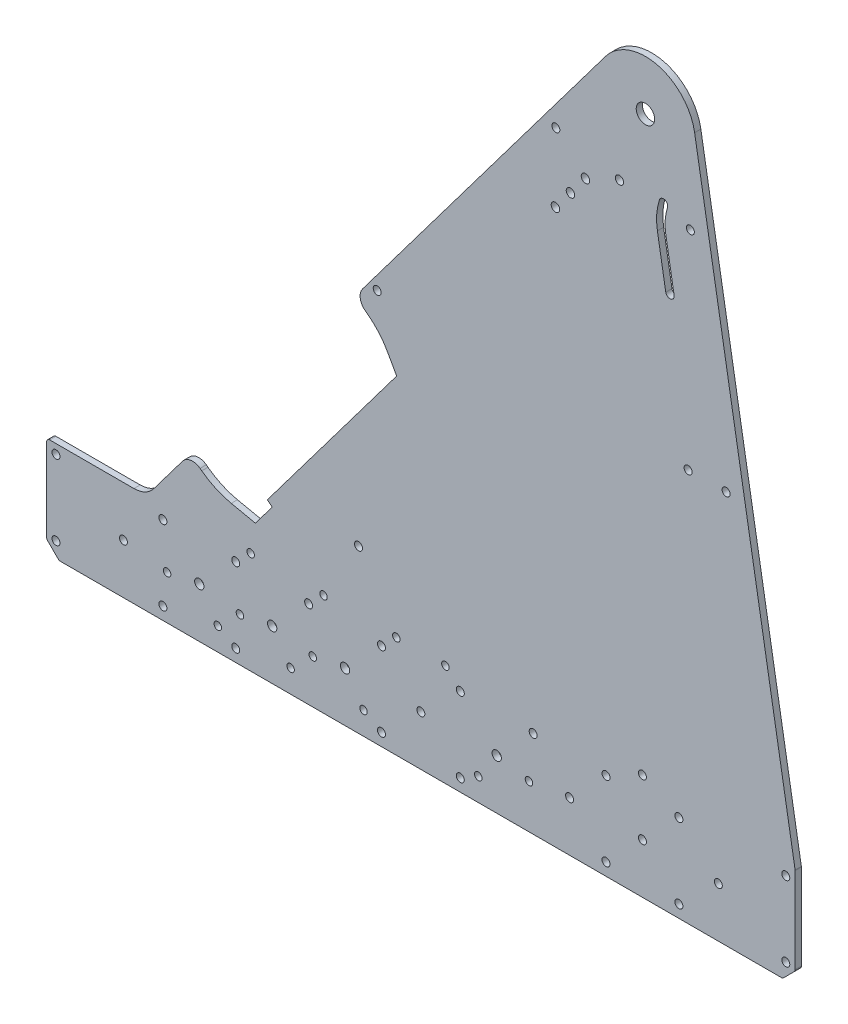
SolidWorks part; units mm, degrees
ref_plane "Front Plane" through (0, 0, 0) normal (0, 0, 1) x (1, 0, 0)
ref_plane "Top Plane" through (0, 0, 0) normal (0, 1, 0) x (1, 0, 0)
ref_plane "Right Plane" through (0, 0, 0) normal (1, 0, 0) x (0, 0, -1)
sketch "Sketch1" plane through (0, 0, 0) normal (0, 0, 1) x (1, 0, 0)
  line L1 (0, 0) -> (381, 0)
  line L2 (0, 0) -> (0, 50.8)
  line L4 (381, 0) -> (381, 50.8)
  line L5 (381, 50.8) -> (329.8374, 350.3513)
  line L6 (0, 50.8) -> (44.463, 50.8)
  line L7 (54.6105, 55.8634) -> (73.025, 80.3327)
  line L9 (112.3265, 79.755) -> (178.1676, 167.245)
  line L11 (157.0275, 191.9556) -> (284.5049, 361.3482)
  line L12 (112.3265, 79.755) -> (114.8634, 77.8458)
  line L13 (114.8634, 77.8458) -> (106.2722, 66.4299)
  line L14 (157.0275, 191.9556) -> (169.7119, 182.4098)
  line L15 (169.7119, 182.4098) -> (178.1676, 167.245)
  line L16 (73.025, 80.3327) -> (85.7094, 70.7869)
  line L17 (85.7094, 70.7869) -> (106.2722, 66.4299)
  line L18 (169.7119, 182.4098) -> (85.7094, 70.7869) construction
  arc A0 (284.5049, 361.3482) -> (329.8374, 350.3513) centre (304.8, 346.075) cw
  arc A1 (44.463, 50.8) -> (54.6105, 55.8634) centre (44.463, 63.5) ccw
  point P11 (50.8, 50.8)
  dimension "D4" = 346.075
  dimension "D7" = 12.7
  dimension "D5" = 25.4
  dimension "D1" = 50.8
  dimension "D2" = 381
  dimension "D3" = 76.2
  dimension "D6" = 50.8
  dimension "D8" = 123.825
  dimension "D9" = 139.7
  dimension "D10" = 15.875
  dimension "D11" = 31.75
  dimension "D12" = 73.025
  dimension "D13" = 3.175
  dimension "D14" = 14.2875
  dimension "D15" = 115
extrude "Boss-Extrude1" add sketch "Sketch1" along normal blind 3.175
sketch "Sketch2" plane through (0, 0, 3.175) normal (0, 0, 1) x (1, 0, 0)
  line L1 (190.5, 50.8) -> (190.5, 0) construction
  line L3 (0, 0) -> (381, 0) construction
  line L5 (0, 6.35) -> (0, 0)
  line L6 (0, 50.8) -> (0, 0) construction
  line L7 (0, 0) -> (6.35, 0)
  line L8 (6.35, 0) -> (0, 6.35)
  line L9 (381, 0) -> (374.65, 0)
  line L10 (374.65, 0) -> (381, 6.35)
  line L11 (381, 6.35) -> (381, 0)
  circle A19 centre (4.7625, 46.0375) radius 2.032
  circle A20 centre (4.7625, 7.9375) radius 2.032
  circle A21 centre (376.2375, 7.9375) radius 2.032
  circle A22 centre (376.2375, 46.0375) radius 2.032
  dimension "D21" = 6.35
  dimension "D27" = 4.064
  dimension "D4" = 46.0375
  dimension "D22" = 6.35
  dimension "D25" = 4.7625
  dimension "D28" = 7.9375
extrude "Cut-Extrude1" cut sketch "Sketch2" against normal up to next
sketch "Sketch5" plane through (0, 0, 3.175) normal (0, 0, 1) x (1, 0, 0)
  line L0 (151.892, 25.4) -> (229.108, 25.4) construction
  line L1 (229.108, 25.4) -> (341.884, 25.4) construction
  circle A0 centre (39.116, 25.4) radius 2.032
  circle A1 centre (59.182, 6.35) radius 2.032
  circle A2 centre (59.182, 44.45) radius 2.032
  circle A3 centre (96.266, 44.45) radius 2.032
  circle A4 centre (133.35, 44.45) radius 2.032
  circle A5 centre (170.434, 44.45) radius 2.032
  circle A6 centre (210.566, 44.45) radius 2.032
  circle A7 centre (210.566, 6.35) radius 2.032
  circle A8 centre (170.434, 6.35) radius 2.032
  circle A9 centre (247.65, 44.45) radius 2.032
  circle A10 centre (266.192, 25.4) radius 2.032
  circle A11 centre (39.116, 25.4) radius 2.286 construction
  circle A12 centre (59.182, 44.45) radius 1.905 construction
  circle A13 centre (59.182, 6.35) radius 1.905 construction
  circle A14 centre (96.266, 44.45) radius 1.905 construction
  circle A15 centre (133.35, 44.45) radius 1.905 construction
  circle A16 centre (170.434, 44.45) radius 1.905 construction
  circle A17 centre (170.434, 6.35) radius 2.159 construction
  circle A18 centre (210.566, 6.35) radius 2.159 construction
  circle A19 centre (210.566, 44.45) radius 1.905 construction
  circle A20 centre (247.65, 44.45) radius 1.905 construction
  circle A21 centre (266.192, 25.4) radius 2.286 construction
  circle A22 centre (77.724, 25.4) radius 2.3813
  circle A23 centre (114.808, 25.4) radius 2.3813
  circle A24 centre (151.892, 25.4) radius 2.3813
  circle A25 centre (229.108, 25.4) radius 2.3813
  circle A26 centre (190.5, 25.4) radius 2.032
  circle A28 centre (303.276, 25.4) radius 2.032
  circle A29 centre (341.884, 25.4) radius 2.032
  circle A30 centre (77.724, 25.4) radius 7.366 construction
  circle A31 centre (114.808, 25.4) radius 7.366 construction
  circle A32 centre (151.892, 25.4) radius 7.366 construction
  circle A33 centre (229.108, 25.4) radius 7.366 construction
  dimension "D1" = 4.064
  dimension "D2" = 4.7625
  dimension "D3" = 37.084
  dimension "D4" = 38.608
  dimension "D5" = 38.608
extrude "Cut-Extrude4" cut sketch "Sketch5" against normal through all
sketch "Sketch6" plane through (0, 0, 3.175) normal (0, 0, 1) x (1, 0, 0)
  line L0 (6.35, 0) -> (374.65, 0) construction
  line L1 (266.192, 25.4) -> (303.276, 25.4) construction
  line L2 (284.734, 6.35) -> (284.734, 44.45) construction
  line L3 (151.892, 25.4) -> (114.808, 25.4) construction
  line L4 (114.808, 25.4) -> (77.724, 25.4) construction
  circle A0 centre (284.734, 44.45) radius 2.032
  circle A1 centre (284.734, 6.35) radius 2.032
  circle A2 centre (321.818, 6.35) radius 2.032
  circle A3 centre (321.818, 44.45) radius 2.032
  circle A4 centre (96.266, 6.35) radius 2.032
  circle A6 centre (303.276, 53.975) radius 2.032
  arc A7 (304.329, 52.3875) -> (302.223, 52.3875) centre (303.276, 53.975) ccw construction
  point P8 (284.734, 25.4)
  point P9 (284.734, 25.4)
  point P28 (96.266, 25.4)
  dimension "D1" = 4.064
  dimension "D2" = 6.35
  dimension "D3" = 37.084
extrude "Cut-Extrude5" cut sketch "Sketch6" against normal through all
sketch "Sketch3" plane through (0, 0, 3.175) normal (0, 0, 1) x (1, 0, 0)
  line L0 (73.025, 80.3327) -> (54.6105, 55.8634) construction
  line L1 (381, 6.35) -> (381, 50.8) construction
  line L2 (6.35, 0) -> (374.65, 0) construction
  line L3 (304.8, 346.075) -> (291.577, 310.3432) construction
  line L4 (274.2689, 302.3851) -> (291.577, 310.3432) construction
  line L5 (274.2689, 302.3851) -> (266.6323, 292.2376) construction
  line L6 (266.6323, 292.2376) -> (258.9957, 282.09) construction
  line L7 (381, 50.8) -> (329.8374, 350.3513) construction
  line L9 (0, 50.8) -> (0, 6.35) construction
  line L14 (284.5049, 361.3482) -> (157.0275, 191.9556) construction
  line L15 (317.2725, 273.05) -> (310.5324, 312.5124) construction
  line L16 (315.1443, 272.6865) -> (310.8903, 297.5932)
  line L17 (319.4007, 273.4135) -> (315.1467, 298.3202)
  circle A0 centre (304.8, 346.075) radius 4.699
  circle A1 centre (168.275, 200.025) radius 2.032
  circle A2 centre (158.75, 82.55) radius 2.032
  circle A3 centre (291.577, 310.3432) radius 2.0955
  circle A5 centre (274.2689, 302.3851) radius 2.159
  circle A6 centre (266.6323, 292.2376) radius 2.159
  circle A7 centre (258.9957, 282.09) radius 2.159
  circle A8 centre (327.6754, 306.4341) radius 2.032
  circle A9 centre (345.8498, 200.025) radius 2.032
  circle A12 centre (259.2118, 317.1783) radius 2.032
  circle A13 centre (326.524, 200.025) radius 2.032
  arc A14 (315.1467, 298.3202) -> (316.0385, 310.4799) centre (340.1841, 302.5965) cw
  arc A19 (315.1443, 272.6865) -> (319.4007, 273.4135) centre (317.2725, 273.05) ccw
  arc A21 (316.0385, 310.4799) -> (311.9337, 311.8201) centre (313.9861, 311.15) ccw
  arc A22 (311.9337, 311.8201) -> (310.8903, 297.5932) centre (340.1841, 302.5965) ccw
  point P41 (313.3855, 298.45)
  dimension "D1" = 9.398
  dimension "D3" = 4.064
  dimension "D6" = 4.064
  dimension "D11" = 4.318
  dimension "D10" = 4.191
  dimension "D13" = 4.064
  dimension "D20" = 4.064
  dimension "D18" = 3.175
  dimension "D34" = 4.318
  dimension "D21" = 25.4
  dimension "D4" = 222.25
  dimension "D5" = 82.55
  dimension "D7" = 19.05
  dimension "D8" = 12.7
  dimension "D9" = 38.1
  dimension "D12" = 12.7
  dimension "D14" = 9.525
  dimension "D15" = 9.525
  dimension "D16" = 107.95
  dimension "D17" = 200.025
  dimension "D19" = 34.925
  dimension "D23" = 53.975
  dimension "D24" = 6.35
  dimension "D25" = 200.025
  dimension "D26" = 168.275
  dimension "D27" = 28.575
  dimension "D30" = 30
  dimension "D31" = 135
  dimension "D33" = 25.4
  dimension "D35" = 273.05
extrude "Cut-Extrude2" cut sketch "Sketch3" against normal through all
fillet "Fillet1" radius 1.5875 6 edges at (374.65, 0, 1.5875) (381, 6.35, 1.5875) (381, 50.8, 1.5875) (6.35, 0, 1.5875) (0, 6.35, 1.5875) (0, 50.8, 1.5875)
sketch "Sketch4" plane through (0, 0, 0) normal (0, 0, -1) x (-1, 0, 0)
  circle A0 centre (-61.3181, 22.2981) radius 1.905 construction
  circle A1 centre (-87.1313, 11.606) radius 1.905 construction
  circle A2 centre (-98.4021, 22.2981) radius 1.905 construction
  circle A3 centre (-124.2153, 11.606) radius 1.905 construction
  circle A4 centre (-135.4861, 22.2981) radius 1.905 construction
  circle A5 centre (-161.2993, 11.606) radius 1.905 construction
  circle A6 centre (-245.5139, 22.2981) radius 1.905 construction
  circle A7 centre (-219.7007, 11.606) radius 1.905 construction
  circle A8 centre (-202.982, 51.9684) radius 1.905 construction
  circle A9 centre (-178.018, 51.9684) radius 1.905 construction
  circle A10 centre (-140.934, 51.9684) radius 1.905 construction
  circle A11 centre (-103.85, 51.9684) radius 1.905 construction
  circle A12 centre (-61.3181, 22.2981) radius 1.905
  circle A13 centre (-87.1313, 11.606) radius 1.905
  circle A14 centre (-98.4021, 22.2981) radius 1.905
  circle A15 centre (-124.2153, 11.606) radius 1.905
  circle A16 centre (-135.4861, 22.2981) radius 1.905
  circle A17 centre (-161.2993, 11.606) radius 1.905
  circle A18 centre (-245.5139, 22.2981) radius 1.905
  circle A19 centre (-219.7007, 11.606) radius 1.905
  circle A20 centre (-202.982, 51.9684) radius 1.905
  circle A21 centre (-178.018, 51.9684) radius 1.905
  circle A22 centre (-140.934, 51.9684) radius 1.905
  circle A23 centre (-103.85, 51.9684) radius 1.905
extrude "Cut-Extrude3" cut sketch "Sketch4" against normal up to next
fillet "Fillet2" radius 38.1 2 edges at (85.7094, 70.7869, 1.5875) (169.7119, 182.4098, 1.5875)
fillet "Fillet3" radius 6.35 2 edges at (73.025, 80.3327, 1.5875) (157.0275, 191.9556, 1.5875)
